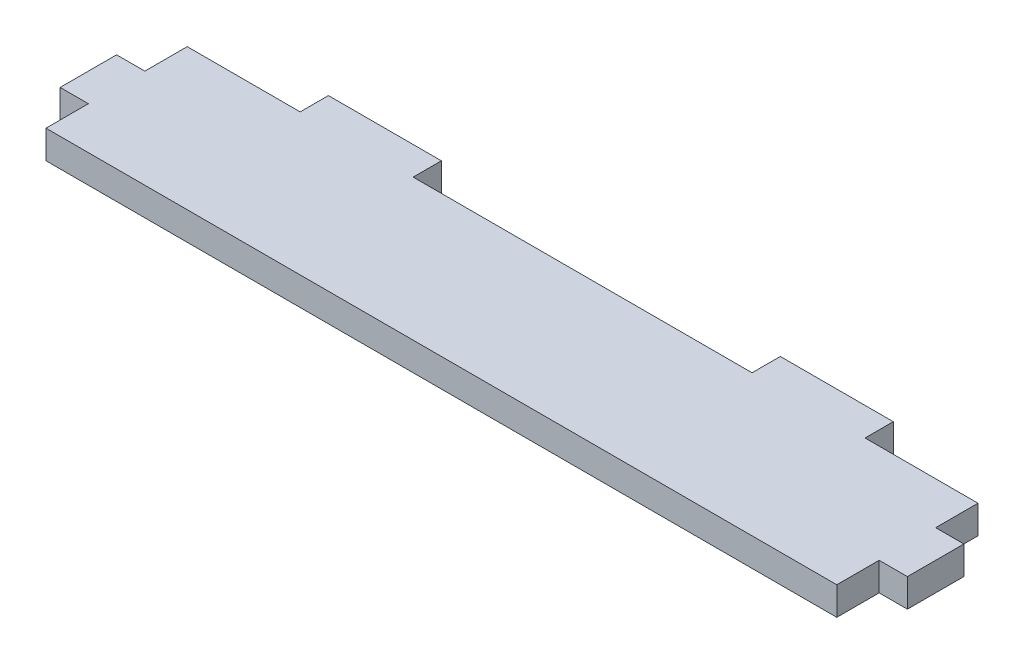
SolidWorks part; units mm, degrees
material "Very Low Density PE (SS)"
ref_plane "Front Plane" through (0, 0, 0) normal (0, 0, 1) x (1, 0, 0)
ref_plane "Top Plane" through (0, 0, 0) normal (0, 1, 0) x (1, 0, 0)
ref_plane "Right Plane" through (0, 0, 0) normal (1, 0, 0) x (0, 0, -1)
sketch "Sketch1" plane through (0, 0, 0) normal (0, 1, 0) x (1, 0, 0)
  line L0 (0, 12.5) -> (0, -12.5) construction
  line L1 (-70, 12.5) -> (-50, 12.5)
  line L2 (-70, 12.5) -> (-70, 5)
  line L3 (-70, -12.5) -> (70, -12.5)
  line L4 (70, 12.5) -> (70, 5)
  line L5 (-70, 12.5) -> (70, -12.5) construction
  line L6 (-70, -12.5) -> (70, 12.5) construction
  line L7 (-50, 12.5) -> (-30, 12.5) construction
  line L8 (-50, 12.5) -> (-50, 17.5)
  line L9 (-50, 17.5) -> (-30, 17.5)
  line L10 (-30, 12.5) -> (-30, 17.5)
  line L11 (50, 17.5) -> (30, 17.5)
  line L12 (30, 12.5) -> (30, 17.5)
  line L13 (50, 12.5) -> (30, 12.5) construction
  line L14 (50, 12.5) -> (50, 17.5)
  line L15 (-50, 12.5) -> (-30, 12.5) construction
  line L16 (-30, 12.5) -> (30, 12.5)
  line L17 (30, 12.5) -> (50, 12.5) construction
  line L18 (50, 12.5) -> (70, 12.5)
  line L19 (75, -5) -> (70, -5)
  line L20 (-75, 5) -> (-70, 5)
  line L21 (-75, 5) -> (-75, -5)
  line L22 (-75, -5) -> (-70, -5)
  line L23 (-70, 5) -> (-70, -5) construction
  line L24 (-75, 5) -> (-70, -5) construction
  line L25 (-75, -5) -> (-70, 5) construction
  line L26 (70, 5) -> (70, -5) construction
  line L27 (75, 5) -> (70, 5)
  line L28 (75, 5) -> (75, -5)
  line L29 (-70, 5) -> (-70, -5) construction
  line L30 (-70, -5) -> (-70, -12.5)
  line L31 (70, 5) -> (70, -5) construction
  line L32 (70, -5) -> (70, -12.5)
  point P0 (0, 0)
  point P17 (-72.5, 0)
  dimension "D1" = 140
  dimension "D2" = 25
  dimension "D3" = 5
  dimension "D4" = 20
  dimension "D5" = 20
  dimension "D6" = 5
  dimension "D7" = 10
extrude "Boss-Extrude1" add sketch "Sketch1" along normal blind 5
